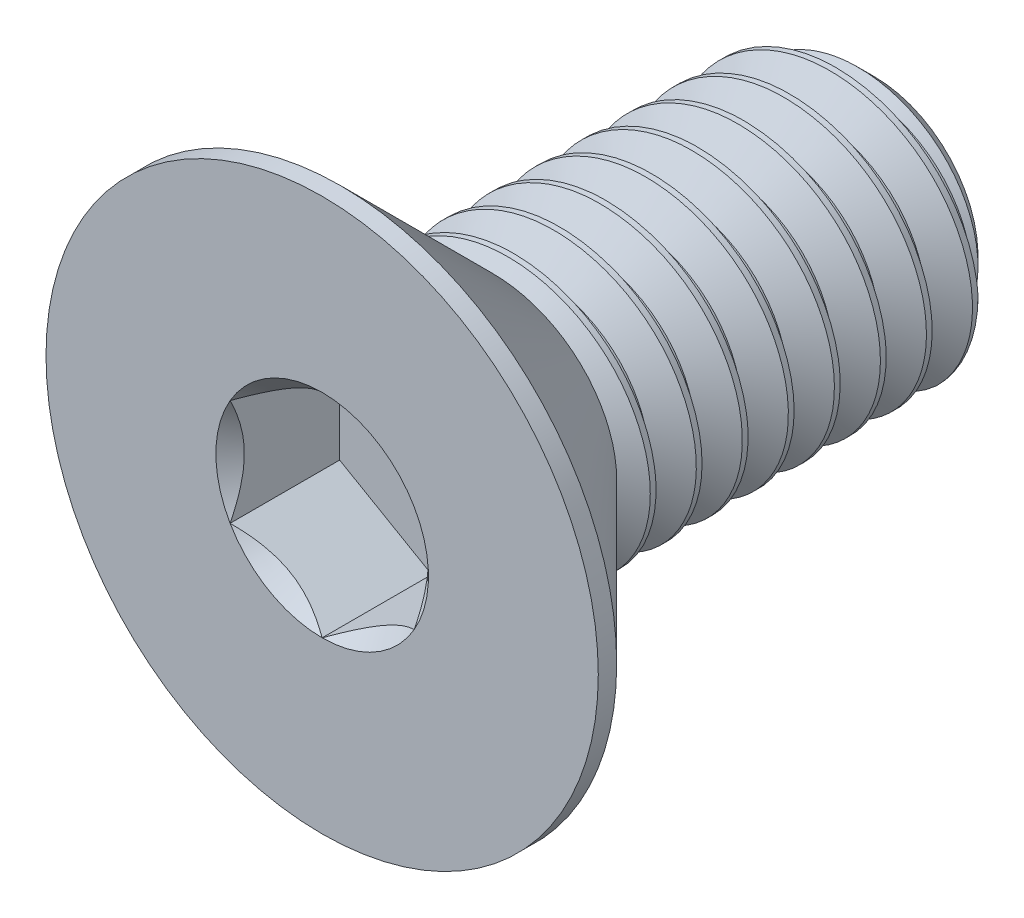
SolidWorks part; units mm, degrees
ref_plane "Front" through (0, 0, 0) normal (0, 0, 1) x (1, 0, 0)
ref_plane "Top" through (0, 0, 0) normal (0, 1, 0) x (1, 0, 0)
ref_plane "Right" through (0, 0, 0) normal (1, 0, 0) x (0, 0, -1)
sketch "Sketch1" plane through (0, 0, 0) normal (1, 0, 0) x (0, 0, -1)
  line L0 (0, 3) -> (0.2, 3) construction
  line L1 (0.2, 3) -> (1.7, 1.5) construction
  line L2 (0, 1.5) -> (6, 1.5)
  line L3 (6, 1.5) -> (6, 0)
  line L4 (6, 0) -> (0, 0)
  line L5 (0, 0) -> (0, 3) construction
  line L6 (0, 3) -> (0, -3) construction
  line L7 (6, 1.5) -> (6, -1.5) construction
  line L8 (0, -3) -> (0.2, -3) construction
  line L9 (0.2, -3) -> (1.7, -1.5) construction
  line L11 (0, 1.5) -> (0, 0)
  line L12 (1.7, 1.5) -> (1.7, 0) construction
  dimension "Head Ht" = 1.7
  dimension "Head Dia" = 6
  dimension "Dia" = 3
  dimension "Lg" = 6
  dimension "Head Angle" = 90
revolve "Revolve1" add sketch "Sketch1" angle 360 mid plane about L4
sketch "Sketch3" plane through (0, 0, -6) normal (0, 0, -1) x (-1, 0, 0)
  circle A0 centre (0, 0) radius 1.5
curve "Helix/Spiral1" pitch 0.5 height 6 radius 1.5 centre (0, 0, -6) axis (0, 0, 1) start towards (0, 1, 0)
sketch "Sketch2" plane through (0, 0, 0) normal (1, 0, 0) x (0, 0, -1)
  line L0 (6, 1.5) -> (6.4375, 1.5)
  line L1 (6.4375, 1.5) -> (6.25, 1.1752)
  line L2 (6.25, 1.1752) -> (6.1875, 1.1752)
  line L3 (6.1875, 1.1752) -> (6, 1.5)
  line L4 (6.0938, 1.3376) -> (6.3437, 1.3376) construction
  dimension "D1" = 60
  dimension "D2" = 0.0625
  dimension "D3" = 0.25
chamfer "Chamfer1" distance 0.375 angle 45 1 edges at (0, 1.5, -6)
sweep "Cut-Sweep1" cut profiles "Sketch2" path "Helix/Spiral1"
sketch "Sketch7" plane through (0, 0, 0) normal (1, 0, 0) x (0, 0, -1)
  line L0 (0, 3) -> (0.2, 3) construction
  line L1 (0.2, 3) -> (1.7, 1.5) construction
  line L2 (0, 3) -> (0.2, 3)
  line L3 (0.2, 3) -> (1.7, 1.5)
  line L4 (1.7, 1.5) -> (1.7, 0) construction
  line L5 (1.7, 1.5) -> (1.7, 0)
  line L7 (0, 0) -> (0, 3) construction
  line L8 (0, 0) -> (0, 3)
  line L9 (0, 0) -> (1.7, 0)
  line L10 (3.3, 0) -> (-3.3, 0) construction
revolve "Revolve2" add sketch "Sketch7" angle 360 mid plane about L9
ref_plane "Plane1" through (0, 0, -1.7) normal (0, 0, 1) x (1, 0, 0)
sketch "Sketch8" plane through (0, 0, -1.7) normal (0, 0, 1) x (1, 0, 0)
  circle A0 centre (0, 0) radius 1.5
extrude "Boss-Extrude1" add sketch "Sketch8" against normal through all draft 45
sketch "Sketch5" plane through (0, 0, 0) normal (0, 0, 1) x (1, 0, 0)
  line L1 (1, -0.5774) -> (1, 0.5774)
  line L2 (1, 0.5774) -> (0, 1.1547)
  line L3 (0, 1.1547) -> (-1, 0.5774)
  line L4 (-1, 0.5774) -> (-1, -0.5774)
  line L5 (-1, -0.5774) -> (0, -1.1547)
  line L6 (0, -1.1547) -> (1, -0.5774)
  circle A0 centre (0, 0) radius 1 construction
  dimension "Hex" = 2
extrude "Cut-Extrude2" cut sketch "Sketch5" against normal blind 1.19
sketch "Sketch6" plane through (0, 0, 0) normal (0, 0, 1) x (1, 0, 0)
  circle A0 centre (0, 0) radius 1.1547
extrude "Cut-Extrude3" cut sketch "Sketch6" against normal blind 1.19 draft 45
sketch "Sketch9" [suppressed] plane through (0, 0, -5.5) normal (0, 0, 1) x (1, 0, 0)
  circle A1 centre (0, 0) radius 5
  circle A2 centre (0, 0) radius 5
  point P0 (0, 5)
  dimension "D1" = 0
extrude "Boss-Extrude2" [suppressed] add sketch "Sketch9" against normal offset from surface (18.5 mm away) 26 up to face at (0, 1.125, -6)
fillet "Fillet1" [suppressed] radius 0.3
sketch "Sketch10" plane through (0, 0, 0) normal (1, 0, 0) x (0, 0, -1)
  line L0 (6, 1.5) -> (6, -1.5) construction
  point P0 (5.25, -1.5)
  dimension "D1" = 0.75
equation "\"D3@Helix/Spiral1\" = \"Lg@Sketch1\""
equation "\"D2@Sketch2\" = \"D4@Helix/Spiral1\" * .125"
equation "\"D3@Sketch2\" = \"D4@Helix/Spiral1\" * .5"
equation "\"D1@Chamfer1\" = \"D4@Helix/Spiral1\" * .75"
equation "\"D1@Cut-Extrude2\" = \"Head Ht@Sketch1\" * .7"
equation "\"D1@Sketch10\" = \"D4@Helix/Spiral1\" * 1.5"
equation "\"D1@Cut-Extrude3\" = \"D1@Cut-Extrude2\""
equation "\"D1@Fillet1\" = \"Dia@Sketch1\" * .1"
